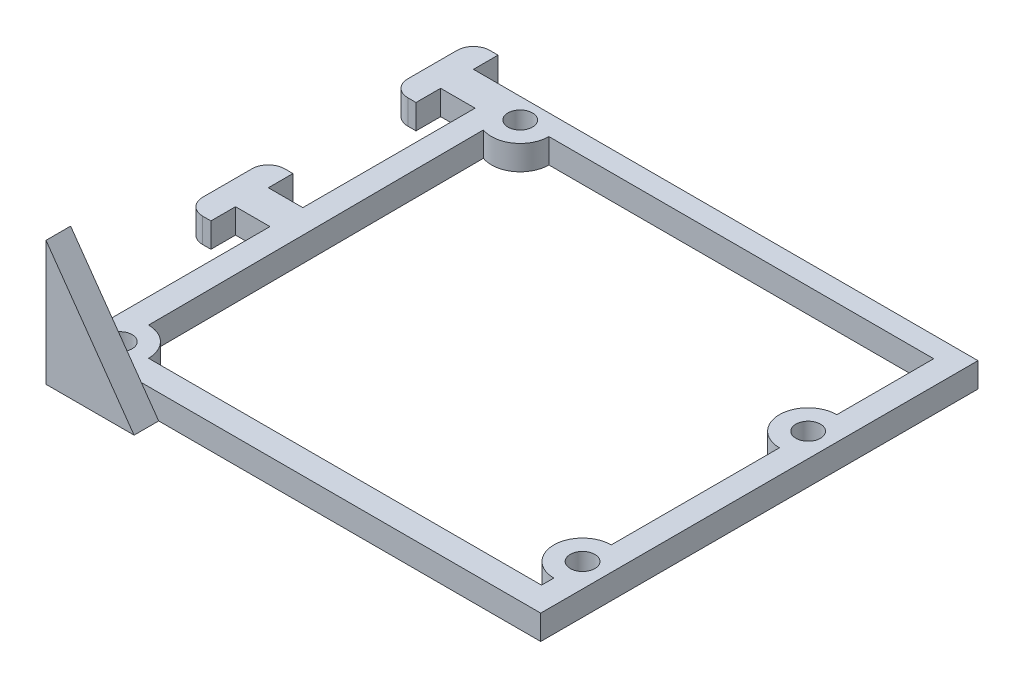
SolidWorks part; units mm, degrees
ref_plane "Front Plane" through (0, 0, 0) normal (0, 0, 1) x (1, 0, 0)
ref_plane "Top Plane" through (0, 0, 0) normal (0, 1, 0) x (1, 0, 0)
ref_plane "Right Plane" through (0, 0, 0) normal (1, 0, 0) x (0, 0, -1)
sketch "Sketch1" plane through (0, 0, 0) normal (0, 1, 0) x (1, 0, 0)
  line L0 (57.3, 5.3) -> (57.3, 0) construction
  line L1 (0, 0) -> (57.3, 0)
  line L2 (0, 0) -> (0, 51.3)
  line L3 (3, 6.5) -> (2.8, 47.5121)
  line L4 (7.5, 50.8) -> (54.4, 50.8)
  line L5 (57.3, 38.3) -> (57.3, 53.3) construction
  line L6 (0, 53.3) -> (57.3, 53.3)
  line L7 (57.3, 53.3) -> (57.3, 0)
  line L8 (54.4, 50.8) -> (54.4, 39)
  line L9 (54.4, 32) -> (54.4, 11.5)
  line L10 (6.5, 3) -> (54.4, 3)
  line L11 (54.4, 3) -> (54.4, 4.5)
  line L12 (2.8, 48.3) -> (2.8, 40.3) construction
  line L13 (0, 53.3) -> (-4.2, 53.3)
  line L14 (-4.2, 53.3) -> (-4.2, 56.3)
  line L15 (-4.2, 56.3) -> (-5.2, 56.3)
  line L16 (-7.2, 54.3) -> (-7.2, 48.3)
  line L17 (-7.2, 51.3) -> (0, 51.3) construction
  line L18 (0, 49.3) -> (-4.2, 49.3)
  line L19 (-4.2, 49.3) -> (-4.2, 46.3)
  line L20 (-4.2, 46.3) -> (-5.2, 46.3)
  line L21 (0, 53.3) -> (0, 51.3)
  circle A0 centre (4, 50.8) radius 1.5
  circle A1 centre (54.4, 35.5) radius 1.5
  circle A2 centre (54.4, 8) radius 1.5
  circle A3 centre (3, 3) radius 1.5
  arc A4 (-7.2, 54.3) -> (-5.2, 56.3) centre (-5.2, 54.3) cw
  arc A5 (2.8, 47.5121) -> (7.5, 50.8) centre (4, 50.8) ccw
  arc A6 (54.4, 39) -> (54.4, 32) centre (54.4, 35.5) ccw
  arc A7 (54.4, 11.5) -> (54.4, 4.5) centre (54.4, 8) ccw
  arc A8 (6.5, 3) -> (3, 6.5) centre (3, 3) ccw
  arc A9 (-7.2, 48.3) -> (-5.2, 46.3) centre (-5.2, 48.3) ccw
  point P42 (-7.2, 56.3)
  dimension "D1" = 3
  dimension "D2" = 3
  dimension "D3" = 3
  dimension "D4" = 3
  dimension "D5" = 4.2
  dimension "D6" = 7
  dimension "D7" = 7
  dimension "D8" = 7
  dimension "D12" = 2
  dimension "D9" = 3
  dimension "D10" = 3
  dimension "D11" = 5
extrude "Boss-Extrude1" add sketch "Sketch1" along normal blind 3 contours L6 L21 L2 L1 L7 A3 A2 A1 A0 L10 A8 L3 A5 L4 L8 A6 L9 A7 L11 region at (0.7826, 0, -24.65)
extrude "Boss-Extrude2" add sketch "Sketch1<3>" along normal blind 3 contours L16 A9 L20 L19 L18 L2 L21 L13 L14 L15 A4 region at (-4.3184, 0, -51.3)
sketch "Sketch1<3>" plane through (0, 0, 0) normal (0, 1, 0) x (1, 0, 0) same geometry as "Sketch1"
pattern_linear "LPattern1" count 2 spacing 25 along (0, 0, 1) of "Boss-Extrude2"
sketch "Sketch2" plane through (0, 0, 0) normal (0, 0, 1) x (1, 0, 0)
  line L0 (0, 0) -> (0, 15.2033)
  line L1 (0, 15.2033) -> (10.7358, 0)
  line L2 (0, 0) -> (57.3, 0) construction
  line L3 (0, 0) -> (10.7358, 0)
extrude "Boss-Extrude3" add sketch "Sketch2" along normal blind 3
